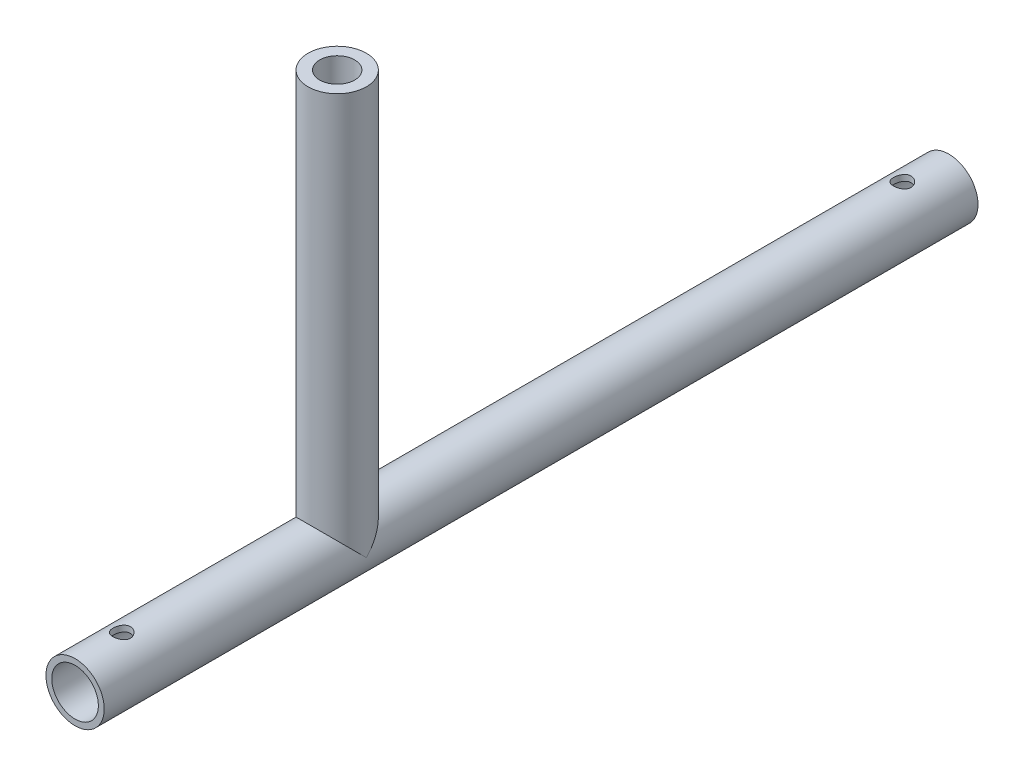
SolidWorks part; units mm, degrees
ref_plane "Ön Düzlem" through (0, 0, 0) normal (0, 0, 1) x (1, 0, 0)
ref_plane "Üst Düzlem" through (0, 0, 0) normal (0, 1, 0) x (1, 0, 0)
ref_plane "Sağ Düzlem" through (0, 0, 0) normal (1, 0, 0) x (0, 0, -1)
sketch "Sketch1" plane through (0, 0, 0) normal (0, 0, 1) x (1, 0, 0)
  circle A0 centre (0, 0) radius 5
  circle A1 centre (0, 0) radius 4
  dimension "D1" = 10
  dimension "D2" = 1
extrude "Boss-Extrude1" add sketch "Sketch1" along normal blind 150
sketch "Sketch2" plane through (0, 0, 0) normal (0, 1, 0) x (1, 0, 0)
  line L0 (5, 0) -> (-5, 0) construction
  line L1 (-4, -150) -> (4, -150) construction
  line L2 (0, -150) -> (0, -247.3876) construction
  line L3 (-5, -150) -> (5, -150) construction
  circle A0 centre (0, -142) radius 1.5
  circle A1 centre (0, -8) radius 1.5
  dimension "D1" = 3
  dimension "D2" = 3
  dimension "D4" = 8
  dimension "D3" = 8
extrude "Cut-Extrude1" cut sketch "Sketch2" against normal blind 21 and the other way blind 21
sketch "Sketch3" plane through (0, 0, 0) normal (0, 1, 0) x (1, 0, 0)
  circle A0 centre (0, -105) radius 5
  dimension "D1" = 10
  dimension "D2" = 105
extrude "Boss-Extrude2" add sketch "Sketch3" along normal blind 60 and the other way up to surface from offset 10 other way up to face at (5, 0, 150)
sketch "Sketch4" plane through (0, 70, 0) normal (0, 1, 0) x (1, 0, 0)
  circle A0 centre (0, -105) radius 3
  dimension "D1" = 6
extrude "Cut-Extrude2" cut sketch "Sketch4" against normal blind 20
